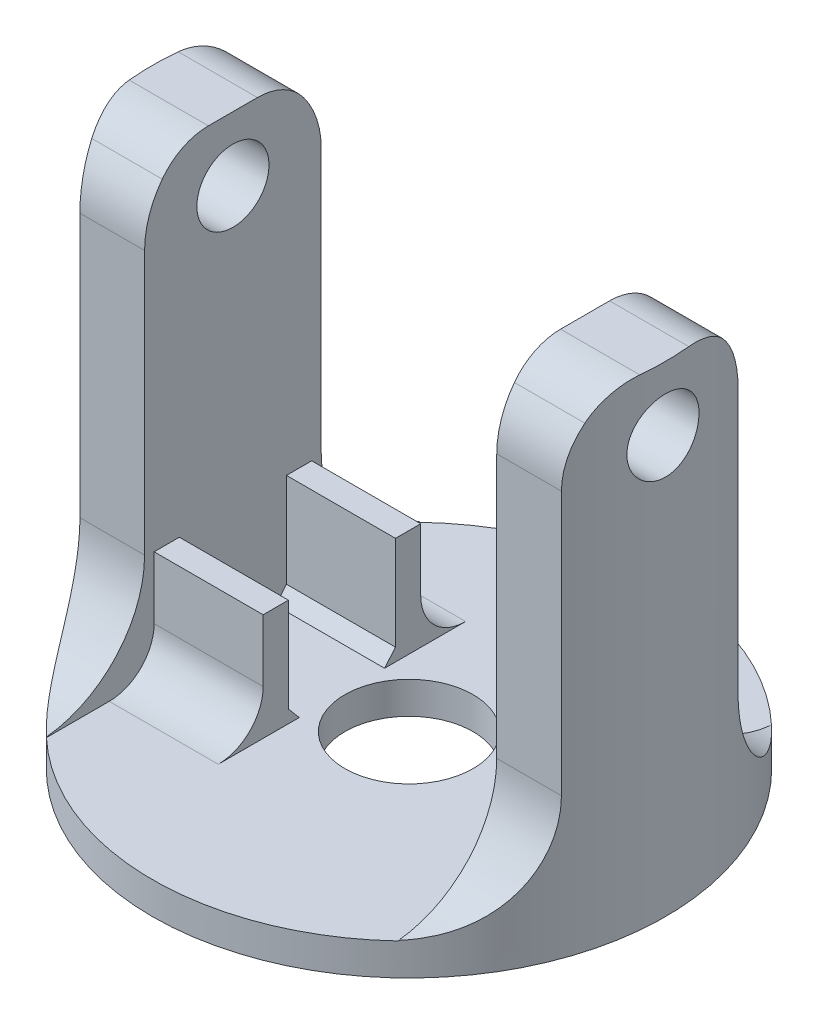
SolidWorks part; units mm, degrees
ref_plane "Front Plane" through (0, 0, 0) normal (0, 0, 1) x (1, 0, 0)
ref_plane "Top Plane" through (0, 0, 0) normal (0, 1, 0) x (1, 0, 0)
ref_plane "Right Plane" through (0, 0, 0) normal (1, 0, 0) x (0, 0, -1)
sketch "Sketch1" plane through (0, 0, 0) normal (0, 1, 0) x (1, 0, 0)
  circle A0 centre (0, 0) radius 101.6
  dimension "D1" = 203.2
extrude "Boss-Extrude1" add sketch "Sketch1" along normal blind 12.7
sketch "Sketch2" plane through (0, 12.7, 0) normal (0, 1, 0) x (1, 0, 0)
  line L0 (0, -148.3769) -> (0, 148.3769) construction
  line L1 (-191.7926, 0) -> (191.7926, 0) construction
  line L2 (69.7492, 34.9877) -> (95.3856, -34.9877) construction
  line L3 (-69.7492, -34.9877) -> (-95.3856, -34.9877)
  line L4 (-69.7492, -34.9877) -> (-69.7492, 34.9877)
  line L5 (-69.7492, 34.9877) -> (-95.3856, 34.9877)
  line L7 (-69.7492, -34.9877) -> (-95.3856, 34.9877) construction
  line L8 (-69.7492, 34.9877) -> (-95.3856, -34.9877) construction
  line L9 (69.7492, -34.9877) -> (95.3856, 34.9877) construction
  line L11 (69.7492, 34.9877) -> (95.3856, 34.9877)
  line L12 (69.7492, -34.9877) -> (95.3856, -34.9877)
  line L13 (69.7492, -34.9877) -> (69.7492, 34.9877)
  circle A0 centre (0, 0) radius 101.6 construction
  arc A1 (-95.3856, 34.9877) -> (-95.3856, -34.9877) centre (0, 0) ccw
  arc A2 (95.3856, -34.9877) -> (95.3856, 34.9877) centre (0, 0) ccw
  point P0 (-82.5674, 0)
  point P4 (0, 0)
  point P8 (0, 0)
  point P19 (82.5674, 0)
extrude "Boss-Extrude3" add sketch "Sketch2" along normal blind 177.8
fillet "Fillet3" radius 43.18 4 edges at (82.5674, 12.7, 34.9877) (82.5674, 12.7, -34.9877) (-82.5674, 12.7, -34.9877) (-82.5674, 12.7, 34.9877)
sketch "Sketch3" plane through (0, 12.7, 0) normal (0, 1, 0) x (1, 0, 0)
  circle A0 centre (0, 0) radius 25.4
  dimension "D1" = 50.8
extrude "Cut-Extrude1" cut sketch "Sketch3" against normal through all
sketch "Sketch4" plane through (69.7492, 0, 0) normal (-1, 0, 0) x (0, 0, 1)
  line L0 (34.9877, 190.5) -> (-34.9877, 190.5) construction
  circle A0 centre (0, 165.1) radius 14.2875
  dimension "D1" = 28.575
  dimension "D2" = 25.4
extrude "Cut-Extrude2" cut sketch "Sketch4" against normal through all and the other way through all
sketch "Sketch5" plane through (69.7492, 0, 0) normal (-1, 0, 0) x (0, 0, 1)
  line L1 (-34.9877, 190.5) -> (-34.9877, 55.88) construction
  line L4 (34.9877, 160.3668) -> (34.9877, 209.9928)
  line L5 (34.9877, 209.9928) -> (-34.9877, 209.9928)
  line L6 (-34.9877, 160.3668) -> (-34.9877, 209.9928)
  line L7 (-20.1605, 188.9622) -> (-34.9877, 209.9928) construction
  line L8 (34.9877, 209.9928) -> (20.1605, 188.9622) construction
  arc A0 (34.9877, 160.3668) -> (-34.9877, 160.3668) centre (0, 160.3668) ccw
extrude "Cut-Extrude3" cut sketch "Sketch5" against normal through all and the other way through all
fillet "Fillet4" radius 22.86 4 edges at (-84.8907, 190.5, 17.7801) (-84.8907, 190.5, -17.7801) (84.8907, 190.5, 17.7801) (84.8907, 190.5, -17.7801)
sketch "Sketch7" plane through (0, 12.7, 0) normal (0, 1, 0) x (1, 0, 0)
  line L0 (-69.7492, -73.8756) -> (-69.7492, 73.8756) construction
  line L1 (-69.7492, 31.209) -> (-26.5692, 31.209)
  line L2 (-69.7492, 31.209) -> (-69.7492, 21.209)
  line L3 (-69.7492, 21.209) -> (-26.5692, 21.209)
  line L4 (-26.5692, 31.209) -> (-26.5692, 21.209)
  line L5 (-48.1592, -21.209) -> (-48.1592, 21.209) construction
  line L6 (-69.7492, -21.209) -> (-26.5692, -21.209)
  line L7 (-69.7492, -21.209) -> (-69.7492, -31.209)
  line L8 (-69.7492, -31.209) -> (-26.5692, -31.209)
  line L9 (-26.5692, -21.209) -> (-26.5692, -31.209)
  line L10 (-48.1592, 0) -> (-69.7492, 0) construction
  point P14 (-69.7492, 0)
  dimension "D1" = 10
  dimension "D2" = 10
  dimension "D3" = 42.418
  dimension "D4" = 43.18
  dimension "D5" = 43.18
  dimension "D6" = 21.209
extrude "Boss-Extrude4" add sketch "Sketch7" along normal blind 42.418
sketch "Sketch8" plane through (-69.7492, 0, 0) normal (1, 0, 0) x (0, 0, -1)
  line L0 (-21.209, 17.78) -> (-21.209, 12.7)
  line L1 (-21.209, 55.118) -> (-21.209, 12.7) construction
  line L2 (-21.209, 12.7) -> (-16.891, 12.7)
  line L3 (-21.209, 12.7) -> (21.209, 12.7) construction
  line L4 (-16.891, 12.7) -> (-21.209, 17.78)
  line L5 (0, 12.7) -> (0, 49.0162) construction
  line L6 (16.891, 12.7) -> (21.209, 17.78)
  line L7 (21.209, 12.7) -> (16.891, 12.7)
  line L8 (21.209, 17.78) -> (21.209, 12.7)
  dimension "D1" = 5.08
  dimension "D2" = 4.318
extrude "Boss-Extrude5" add sketch "Sketch8" along normal up to surface (43.18 mm away) up to face at (-26.5692, 33.909, -26.209)
fillet "Fillet5" radius 17.78 2 edges at (-48.1592, 12.7, 31.209) (-48.1592, 12.7, -31.209)
